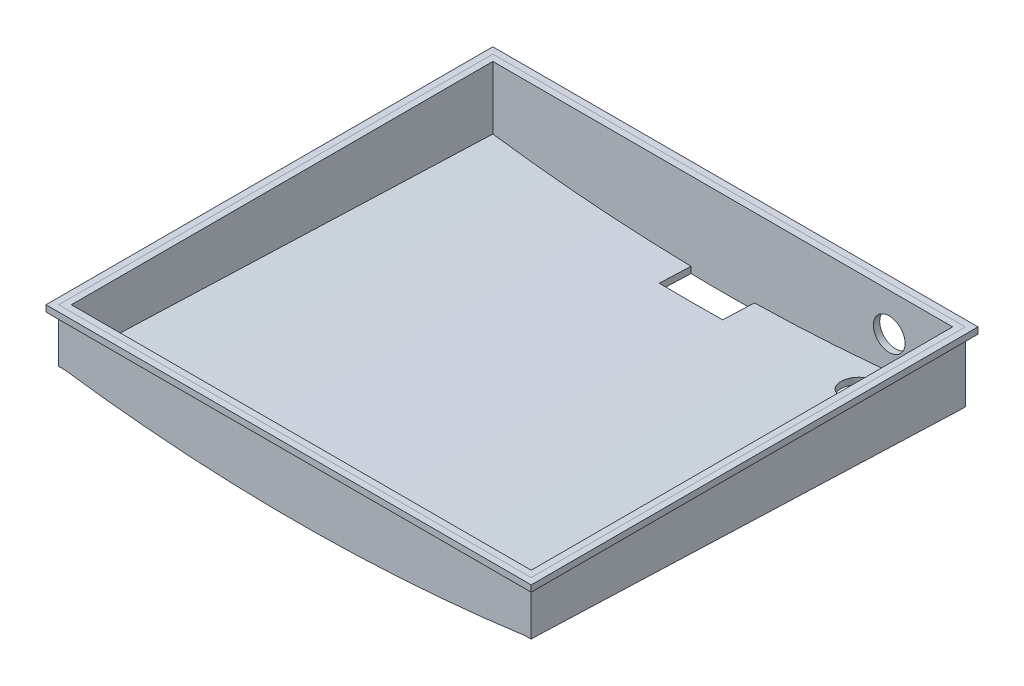
SolidWorks part; units mm, degrees
ref_plane "Front Plane" through (0, 0, 0) normal (0, 0, 1) x (1, 0, 0)
ref_plane "Top Plane" through (0, 0, 0) normal (0, 1, 0) x (1, 0, 0)
ref_plane "Right Plane" through (0, 0, 0) normal (1, 0, 0) x (0, 0, -1)
sketch "Sketch1" plane through (0, 0, 0) normal (0, 0, 1) x (1, 0, 0)
  line L0 (0, 0) -> (-72.5, 0) construction
  line L1 (0, 0) -> (72.5, 0) construction
  line L2 (0, 0) -> (0, -4.9658) construction
  line L3 (72.5, 0) -> (72.5, -2.0188)
  line L4 (-72.5, 0) -> (-72.5, -2.0188)
  arc A0 (72.5, 0) -> (-72.5, 0) centre (0, 526.7671) cw
  arc A1 (72.5, -2.0188) -> (-72.5, -2.0188) centre (0, 526.7671) cw
  arc A3 (72.7727, -1.9813) -> (-72.7727, -1.9813) centre (0, 526.7671) cw construction
  dimension "D1" = 2
sketch "Sketch2" plane through (0, 0, 0) normal (1, 0, 0) x (0, 0, -1)
  line L0 (0, 0) -> (133, 0) construction
  line L2 (133, 0) -> (133, -5) construction
  line L3 (133, -5) -> (0, 0) construction
extrude "Boss-Extrude1" add sketch "Sketch1" along direction (0, 0.0376, 0.9993) on the side against the normal blind 133
sketch "Sketch3" plane through (-72.5, 0, 0) normal (-1, 0, 0) x (0, 0, 1)
  line L0 (-132.9061, -4.9965) -> (-132.9061, 14.8275)
  line L1 (-132.9061, 14.8275) -> (0, 14.8275)
  line L2 (0, 14.8275) -> (0, -2.0188)
  line L3 (0, -2.0188) -> (-132.9061, -7.0153)
  line L4 (-132.9061, -7.0153) -> (-132.9061, -4.9965)
extrude "Boss-Extrude2" add sketch "Sketch3" along normal blind 2
pattern_linear "LPattern1" count 2 spacing 147 along (1, 0, 0) of "Boss-Extrude2"
sketch "Sketch6" plane through (0, 0, 0) normal (0, 0, 1) x (1, 0, 0)
  line L0 (-72.5, 14.8275) -> (72.5, 14.8275)
  line L9 (-72.5, 0) -> (-72.5, 14.8275)
  line L10 (-72.5, 14.8275) -> (-74.5, 14.8275)
  line L11 (-74.5, 14.8275) -> (-74.5, -2.0188)
  line L12 (-74.5, -2.0188) -> (-72.5, -2.0188)
  line L13 (72.5, -2.0188) -> (74.5, -2.0188)
  line L14 (74.5, -2.0188) -> (74.5, 14.8275)
  line L15 (74.5, 14.8275) -> (72.5, 14.8275)
  line L16 (72.5, 14.8275) -> (72.5, 0)
  line L18 (-72.5, 14.8275) -> (-74.5, 14.8275)
  line L19 (-74.5, 14.8275) -> (-74.5, -2.0188)
  line L20 (-74.5, -2.0188) -> (-72.5, -2.0188)
  line L21 (72.5, -2.0188) -> (74.5, -2.0188)
  line L22 (74.5, -2.0188) -> (74.5, 14.8275)
  line L23 (74.5, 14.8275) -> (72.5, 14.8275)
  arc A2 (-72.5, 0) -> (72.5, 0) centre (0, 526.7671) ccw
  arc A3 (-72.5, -2.0188) -> (72.5, -2.0188) centre (0, 526.7671) ccw
  arc A5 (-72.5, -2.0188) -> (72.5, -2.0188) centre (0, 526.7671) ccw
  dimension "D1" = 0
extrude "Boss-Extrude3" add sketch "Sketch6" along normal blind 2
sketch "Sketch7" plane through (0, 0, -132.9061) normal (0, 0, -1) x (-1, 0, 0)
  line L0 (-72.5, 14.8275) -> (72.5, 14.8275)
  line L9 (-72.5, -4.9965) -> (-72.5, 14.8275)
  line L10 (-72.5, 14.8275) -> (-74.5, 14.8275)
  line L11 (-74.5, 14.8275) -> (-74.5, -7.0153)
  line L12 (-74.5, -7.0153) -> (-72.5, -7.0153)
  line L13 (72.5, -7.0153) -> (74.5, -7.0153)
  line L14 (74.5, -7.0153) -> (74.5, 14.8275)
  line L15 (74.5, 14.8275) -> (72.5, 14.8275)
  line L16 (72.5, 14.8275) -> (72.5, -4.9965)
  line L18 (-72.5, 14.8275) -> (-74.5, 14.8275)
  line L19 (-74.5, 14.8275) -> (-74.5, -7.0153)
  line L20 (-74.5, -7.0153) -> (-72.5, -7.0153)
  line L21 (72.5, -7.0153) -> (74.5, -7.0153)
  line L22 (74.5, -7.0153) -> (74.5, 14.8275)
  line L23 (74.5, 14.8275) -> (72.5, 14.8275)
  arc A2 (-72.5, -4.9965) -> (72.5, -4.9965) centre (0, 521.7707) ccw
  arc A3 (-72.5, -7.0153) -> (72.5, -7.0153) centre (0, 521.7707) ccw
  arc A5 (-72.5, -7.0153) -> (72.5, -7.0153) centre (0, 521.7707) ccw
  dimension "D1" = 0
extrude "Boss-Extrude4" add sketch "Sketch7" along normal blind 2
ref_plane "Plane1" through (74.5, 14.8275, 2) normal (0, 0, -1) x (-1, 0, 0)
ref_plane "Plane2" through (0, 14.8275, 0) normal (0, 1, 0) x (1, 0, 0)
sketch "Sketch10" plane through (0, 14.8275, 0) normal (0, 1, 0) x (1, 0, 0)
  line L0 (112.1492, -2) -> (36.8508, -2) construction
  line L1 (-74.5, 134.9061) -> (74.5, 134.9061)
  line L2 (-74.5, 134.9061) -> (-74.5, -2)
  line L3 (-74.5, -2) -> (74.5, -2)
  line L4 (74.5, 134.9061) -> (74.5, -2)
  line L5 (74.5, -2) -> (74.5, 134.9061) construction
  line L6 (-76.5, 136.9061) -> (-76.5, -4)
  line L7 (-76.5, -4) -> (76.5, -4)
  line L8 (76.5, 136.9061) -> (76.5, -4)
  line L9 (-76.5, 136.9061) -> (76.5, 136.9061)
  dimension "D1" = 2
extrude "Boss-Extrude5" add sketch "Sketch10" against normal blind 2 separate body
sketch "Sketch11" plane through (0, 14.8275, 0) normal (0, 1, 0) x (1, 0, 0)
  line L0 (0, 133) -> (0, 0) construction
  line L1 (10, 122.9061) -> (-10, 122.9061)
  line L2 (10, 122.9061) -> (10, 132.9061)
  line L3 (10, 132.9061) -> (-10, 132.9061)
  line L4 (-10, 122.9061) -> (-10, 132.9061)
  line L5 (10, 122.9061) -> (-10, 132.9061) construction
  line L6 (10, 132.9061) -> (-10, 122.9061) construction
  line L7 (-72.5, 132.9061) -> (72.5, 132.9061) construction
  point P0 (0, 127.9061)
extrude "Cut-Extrude1" cut sketch "Sketch11" against normal through all
sketch "Sketch12" plane through (0, 14.8275, 0) normal (0, 1, 0) x (1, 0, 0)
  line L0 (-72.5, 132.9061) -> (-10, 132.9061) construction
  line L1 (72.5, 132.9061) -> (72.5, 0) construction
  circle A0 centre (52.5, 122.9061) radius 5
  dimension "D1" = 10
  dimension "D2" = 20
extrude "Cut-Extrude2" cut sketch "Sketch12" against normal through all
sketch "Sketch13" plane through (74.5, 14.8275, 2) normal (0, 0, -1) x (-1, 0, 0)
  line L0 (2, -21.8427) -> (2, -16.8463) construction
  line L1 (151, -2) -> (-2, -2) construction
  circle A0 centre (22, -12) radius 5
  dimension "D1" = 20
  dimension "D2" = 10
ref_plane "Plane3" through (0, 0, -134.9061) normal (0, 0, -1) x (-1, 0, 0)
sketch "Sketch14" plane through (0, 0, -134.9061) normal (0, 0, -1) x (-1, 0, 0)
  circle A0 centre (-52.5, 2.8275) radius 5
extrude "Cut-Extrude3" cut sketch "Sketch14" against normal up to next (2 mm away)
